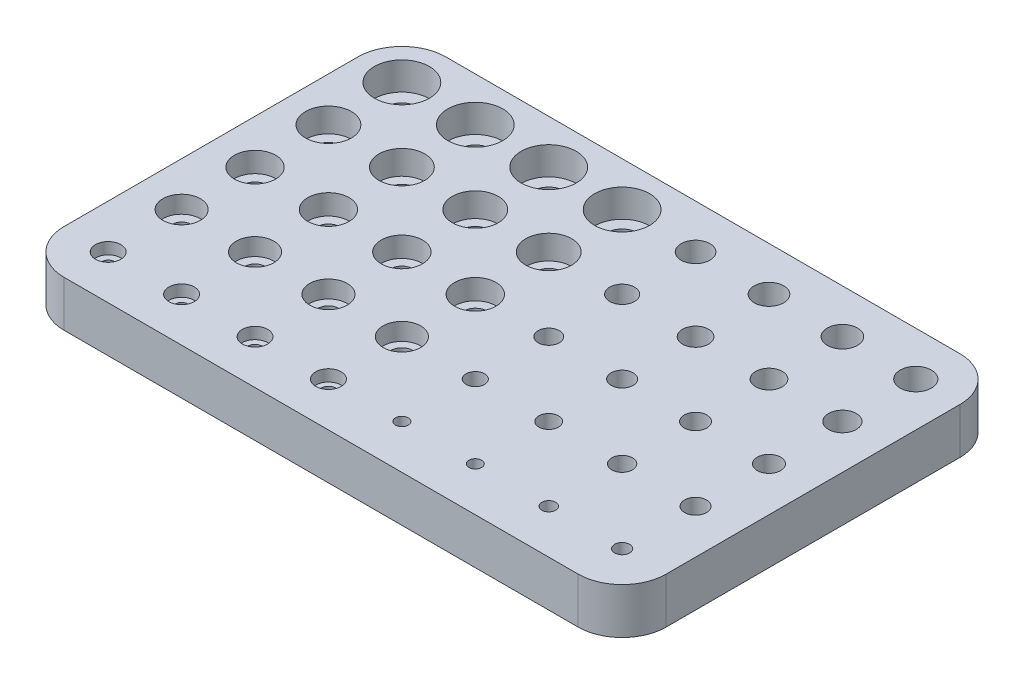
SolidWorks part; units mm, degrees
ref_plane "Front Plane" through (0, 0, 0) normal (0, 0, 1) x (1, 0, 0)
ref_plane "Top Plane" through (0, 0, 0) normal (0, 1, 0) x (1, 0, 0)
ref_plane "Right Plane" through (0, 0, 0) normal (1, 0, 0) x (0, 0, -1)
sketch "Sketch1" plane through (0, 0, 0) normal (0, 1, 0) x (1, 0, 0)
  line L0 (20.32, 7.62) -> (7.62, 7.62) construction
  line L1 (0, 0) -> (53.34, 0)
  line L2 (0, 0) -> (0, 66.04)
  line L3 (0, 66.04) -> (53.34, 66.04)
  line L4 (53.34, 0) -> (53.34, 66.04)
  line L5 (7.62, 7.62) -> (7.62, 20.32) construction
  line L6 (7.62, 7.62) -> (20.32, 7.62) construction
  circle A1 centre (20.32, 58.42) radius 2.5527
  circle A2 centre (33.02, 58.42) radius 2.6098
  circle A3 centre (45.72, 58.42) radius 2.7051
  circle A4 centre (45.72, 45.72) radius 2.4003
  circle A5 centre (33.02, 45.72) radius 2.3114
  circle A6 centre (20.32, 45.72) radius 2.2479
  circle A9 centre (20.32, 33.02) radius 1.8987
  circle A10 centre (33.02, 33.02) radius 1.9558
  circle A11 centre (45.72, 33.02) radius 2.0193
  circle A12 centre (45.72, 20.32) radius 1.9
  circle A13 centre (33.02, 20.32) radius 1.8
  circle A14 centre (20.32, 20.32) radius 1.7
  circle A16 centre (20.32, 7.62) radius 1.1
  circle A18 centre (33.02, 7.62) radius 1.2
  circle A19 centre (45.72, 7.62) radius 1.3
  circle A20 centre (7.62, 58.42) radius 2.4892
  circle A21 centre (7.62, 45.72) radius 2.1526
  circle A22 centre (7.62, 33.02) radius 1.8288
  circle A23 centre (7.62, 7.62) radius 1.1
  circle A24 centre (7.62, 20.32) radius 1.6
  point P4 (7.62, 7.62)
  point P7 (20.32, 7.62)
  point P9 (33.02, 7.62)
  point P10 (45.72, 7.62)
  point P11 (20.32, 20.32)
  point P12 (33.02, 20.32)
  point P13 (45.72, 20.32)
  point P14 (20.32, 33.02)
  point P15 (33.02, 33.02)
  point P16 (45.72, 33.02)
  point P17 (20.32, 45.72)
  point P18 (33.02, 45.72)
  point P19 (45.72, 45.72)
  point P20 (20.32, 58.42)
  point P21 (33.02, 58.42)
  point P22 (45.72, 58.42)
  point P23 (7.62, 20.32)
  point P24 (7.62, 33.02)
  point P25 (7.62, 45.72)
  point P26 (7.62, 58.42)
  point P65 (7.6185, 7.62)
  dimension "D8" = 5.1054
  dimension "D9" = 5.2197
  dimension "D10" = 5.4102
  dimension "D11" = 4.6228
  dimension "D12" = 4.8006
  dimension "D13" = 4.4958
  dimension "D14" = 3.7973
  dimension "D15" = 3.9116
  dimension "D16" = 4.0386
  dimension "D17" = 3.4
  dimension "D18" = 3.6
  dimension "D19" = 3.8
  dimension "D20" = 2.2
  dimension "D21" = 2.4
  dimension "D22" = 2.6
  dimension "D23" = 4.9784
  dimension "D24" = 3.2
  dimension "D25" = 2.2
  dimension "D26" = 3.6576
  dimension "D27" = 4.3053
  dimension "D1" = 4
  dimension "D2" = 5
  dimension "D3" = 7.62
  dimension "D4" = 7.62
  dimension "D5" = 7.62
  dimension "D6" = 7.62
  dimension "D7" = 12.7
extrude "Boss-Extrude1" add sketch "Sketch1" against normal blind 7.9375
pattern_linear "LPattern1" count 2 spacing 50.8 along (1, 0, 0) of bodies 101
combine bodies "Combine1" operation type add bodies to combine 107 101
hole_wizard "CBORE for #10 Socket Head Cap Screw1" positions "Sketch2" profile "Sketch3" counterbore size "#10" standard "ANSI Inch" end condition through all
sketch "Sketch2" plane through (0, 0, 0) normal (0, 1, 0) x (1, 0, 0)
  point P0 (7.62, 58.42)
  point P4 (20.32, 58.42)
  point P7 (33.02, 58.42)
  point P10 (45.72, 58.42)
sketch "Sketch3" plane through (7.62, 0, -58.42) normal (1, 0, 0) x (0, 0, 1)
  line L0 (0, 0) -> (0, 7.9375)
  line L1 (0, 7.9375) -> (2.4892, 7.9375)
  line L3 (2.4892, 7.9375) -> (2.4892, 4.826)
  line L4 (2.4892, 4.826) -> (4.7625, 4.826)
  line L5 (4.7625, 4.826) -> (4.7625, 0)
  line L7 (4.7625, 0) -> (0, 0)
  line L11 (0, -6.35) -> (0, 107.95) construction
  dimension "Thru Hole Dia." = 4.9784
  dimension "Thru Hole Depth" = 7.9375
  dimension "C'Bore Dia." = 9.525
  dimension "C'Bore Depth" = 4.826
hole_wizard "CBORE for #8 Socket Head Cap Screw1" positions "Sketch4" profile "Sketch5" counterbore size "#8" standard "ANSI Inch" end condition through all
sketch "Sketch4" plane through (0, 0, 0) normal (0, 1, 0) x (1, 0, 0)
  point P0 (7.62, 45.72)
  point P3 (20.32, 45.72)
  point P6 (33.02, 45.72)
  point P9 (45.72, 45.72)
sketch "Sketch5" plane through (7.62, 0, -45.72) normal (1, 0, 0) x (0, 0, 1)
  line L0 (0, 0) -> (0, 7.9375)
  line L1 (0, 7.9375) -> (2.1526, 7.9375)
  line L3 (2.1526, 7.9375) -> (2.1526, 4.1656)
  line L4 (2.1526, 4.1656) -> (3.9687, 4.1656)
  line L5 (3.9687, 4.1656) -> (3.9687, 0)
  line L7 (3.9687, 0) -> (0, 0)
  line L11 (0, -6.35) -> (0, 107.95) construction
  dimension "Thru Hole Dia." = 4.3053
  dimension "Thru Hole Depth" = 7.9375
  dimension "C'Bore Dia." = 7.9375
  dimension "C'Bore Depth" = 4.1656
hole_wizard "CBORE for #6 Socket Head Cap Screw1" positions "Sketch6" profile "Sketch7" counterbore size "#6" standard "ANSI Inch" end condition through all
sketch "Sketch6" plane through (0, 0, 0) normal (0, 1, 0) x (1, 0, 0)
  point P0 (7.62, 33.02)
  point P3 (20.32, 33.02)
  point P6 (33.02, 33.02)
  point P9 (45.72, 33.02)
sketch "Sketch7" plane through (7.62, 0, -33.02) normal (1, 0, 0) x (0, 0, 1)
  line L0 (0, 0) -> (0, 7.9375)
  line L1 (0, 7.9375) -> (1.8288, 7.9375)
  line L3 (1.8288, 7.9375) -> (1.8288, 3.5052)
  line L4 (1.8288, 3.5052) -> (3.5725, 3.5052)
  line L5 (3.5725, 3.5052) -> (3.5725, 0)
  line L7 (3.5725, 0) -> (0, 0)
  line L11 (0, -6.35) -> (0, 107.95) construction
  dimension "Thru Hole Dia." = 3.6576
  dimension "Thru Hole Depth" = 7.9375
  dimension "C'Bore Dia." = 7.145
  dimension "C'Bore Depth" = 3.5052
hole_wizard "CBORE for M3 SHCS1" positions "Sketch8" profile "Sketch9" counterbore size "M3" standard "ANSI Metric" end condition through all
sketch "Sketch8" plane through (0, 0, 0) normal (0, 1, 0) x (1, 0, 0)
  point P0 (7.62, 20.32)
  point P3 (20.32, 20.32)
  point P6 (33.02, 20.32)
  point P9 (45.72, 20.32)
sketch "Sketch9" plane through (7.62, 0, -20.32) normal (1, 0, 0) x (0, 0, 1)
  line L0 (0, 0) -> (0, 7.9375)
  line L1 (0, 7.9375) -> (1.6, 7.9375)
  line L3 (1.6, 7.9375) -> (1.6, 3)
  line L4 (1.6, 3) -> (3.25, 3)
  line L5 (3.25, 3) -> (3.25, 0)
  line L7 (3.25, 0) -> (0, 0)
  line L11 (0, -6.35) -> (0, 107.95) construction
  dimension "Thru Hole Dia." = 3.2
  dimension "Thru Hole Depth" = 7.9375
  dimension "C'Bore Dia." = 6.5
  dimension "C'Bore Depth" = 3
hole_wizard "CBORE for M2 SHCS1" positions "Sketch10" profile "Sketch11" counterbore size "M2" standard "ANSI Metric" end condition through all
sketch "Sketch10" plane through (0, 0, 0) normal (0, 1, 0) x (1, 0, 0)
  point P0 (7.62, 7.62)
  point P3 (20.32, 7.62)
  point P6 (33.02, 7.62)
  point P9 (45.72, 7.62)
sketch "Sketch11" plane through (7.62, 0, -7.62) normal (1, 0, 0) x (0, 0, 1)
  line L0 (0, 0) -> (0, 7.9375)
  line L1 (0, 7.9375) -> (1.1, 7.9375)
  line L3 (1.1, 7.9375) -> (1.1, 2)
  line L4 (1.1, 2) -> (2.2, 2)
  line L5 (2.2, 2) -> (2.2, 0)
  line L7 (2.2, 0) -> (0, 0)
  line L11 (0, -6.35) -> (0, 107.95) construction
  dimension "Thru Hole Dia." = 2.2
  dimension "Thru Hole Depth" = 7.9375
  dimension "C'Bore Dia." = 4.4
  dimension "C'Bore Depth" = 2
fillet "Fillet1" radius 7.62 4 edges at (104.14, -3.9688, -66.04) (104.14, -3.9688, 0) (0, -3.9688, -66.04) (0, -3.9688, 0)
